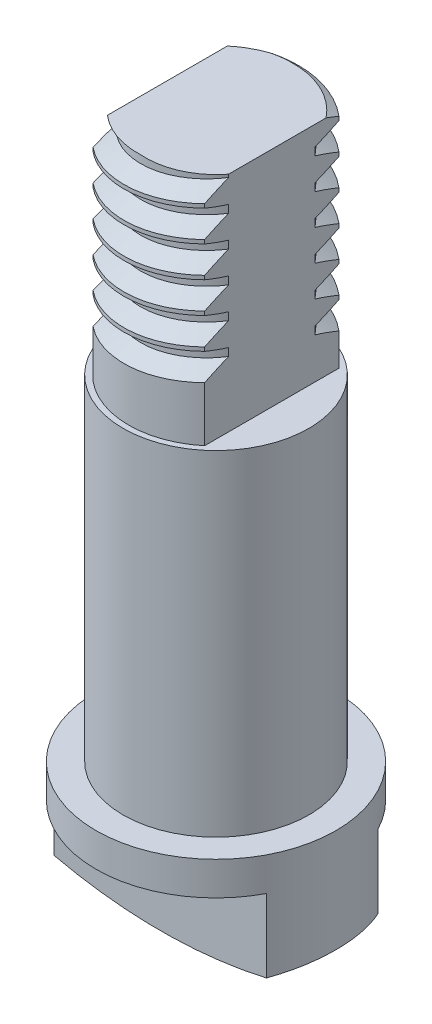
SolidWorks part; units mm, degrees
material "Brass"
ref_plane "Front Plane" through (0, 0, 0) normal (0, 0, 1) x (1, 0, 0)
ref_plane "Top Plane" through (0, 0, 0) normal (0, 1, 0) x (1, 0, 0)
ref_plane "Right Plane" through (0, 0, 0) normal (1, 0, 0) x (0, 0, -1)
sketch "Sketch1" plane through (0, 0, 0) normal (0, 1, 0) x (1, 0, 0)
  circle A0 centre (0, 0) radius 5.461
  dimension "D1" = 10.922
extrude "Boss-Extrude1" add sketch "Sketch1" along normal blind 1.524
sketch "Sketch2" plane through (0, 1.524, 0) normal (0, 1, 0) x (1, 0, 0)
  circle A0 centre (0, 0) radius 4.2291
  dimension "D1" = 8.4582
extrude "Boss-Extrude2" add sketch "Sketch2" along normal blind 25.4
sketch "Sketch3" plane through (0, 26.924, 0) normal (0, 1, 0) x (1, 0, 0)
  circle A0 centre (0, 0) radius 4.2291
  circle A1 centre (0, 0) radius 3.9751
  dimension "D1" = 0.254
extrude "Cut-Extrude1" cut sketch "Sketch3" against normal blind 10.16 contours A0 | A1
thread "Thread1" pitch 1.4111 method cut profile "Thread Profile1" start angle 0, offset 1.27, length 14.0538, pitch 1.4111, diameter 7.9502
ref_plane "Plane1" through (3.9751, 18.034, 0) normal (0, 0, 1) x (1, 0, 0)
sketch "Thread Profile1" plane through (3.9751, 18.034, 0) normal (0, 0, 1) x (1, 0, 0)
  line L0 (0, 0) -> (0, 1.4111) construction
  line L11 (0, 0) -> (0, 1.2347)
  line L12 (0, 1.2347) -> (-0.7638, 0.7937)
  line L13 (-0.7638, 0.7937) -> (-0.7638, 0.441)
  line L15 (-0.7638, 0.441) -> (0, 0)
  line L17 (-0.7638, 0.6174) -> (0, 0.6174) construction
  point P2 (0, 0)
  dimension "Pitch" = 1.4111
  dimension "Profile_Angle" = 60
  dimension "Profile_Land" = 0.3528
  dimension "Profile_Height" = 0.7638
sketch "Sketch6" plane through (0, 26.924, 0) normal (0, 1, 0) x (1, 0, 0)
  line L0 (-2.54, -5.08) -> (-2.54, 5.08)
  line L3 (2.54, -5.08) -> (2.54, 5.08)
  line L4 (-2.54, -5.08) -> (2.54, 5.08) construction
  line L5 (-2.54, 5.08) -> (2.54, -5.08) construction
  arc A0 (-2.54, 5.08) -> (-2.54, -5.08) centre (0, 0) ccw
  arc A1 (2.54, -5.08) -> (2.54, 5.08) centre (0, 0) ccw
  point P1 (0, 0)
  dimension "D1" = 5.08
  dimension "D2" = 10.16
extrude "Cut-Extrude2" cut sketch "Sketch6" against normal blind 10.16
sketch "Sketch7" plane through (0, 0, 0) normal (0, 0, 1) x (1, 0, 0)
  line L0 (-5.461, 0) -> (5.461, 0) construction
  line L1 (-5.461, 0) -> (5.461, 0)
  line L2 (-5.461, 0) -> (-5.461, -3.175)
  line L4 (5.461, 0) -> (5.461, -3.175)
  line L5 (2.54, 16.764) -> (-2.54, 16.764) construction
  arc A0 (-5.461, -3.175) -> (5.461, -3.175) centre (0, 17.7129) ccw
  dimension "D2" = 21.59
  dimension "D3" = 0.9489
  dimension "D4" = 5.461
  dimension "D1" = 3.175
  dimension "D5" = 10.922
extrude "Boss-Extrude3" add sketch "Sketch7" along normal mid plane 5.08
sketch "Sketch8" plane through (0, 1.524, 0) normal (0, 1, 0) x (1, 0, 0)
  circle A0 centre (0, 0) radius 5.461
  circle A1 centre (0, 0) radius 7.3123
extrude "Cut-Extrude3" cut sketch "Sketch8" against normal blind 5.08
